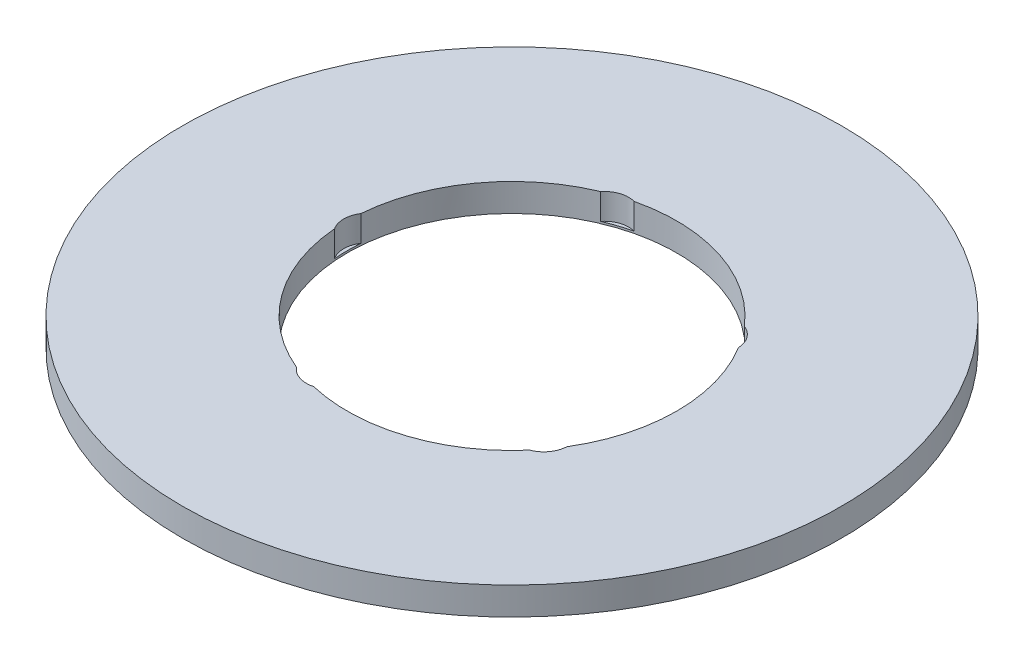
SolidWorks part; units mm, degrees
ref_plane "Front Plane" through (0, 0, 0) normal (0, 0, 1) x (1, 0, 0)
ref_plane "Top Plane" through (0, 0, 0) normal (0, 1, 0) x (1, 0, 0)
ref_plane "Right Plane" through (0, 0, 0) normal (1, 0, 0) x (0, 0, -1)
sketch "Sketch1" plane through (0, 0, 0) normal (0, 1, 0) x (1, 0, 0)
  circle A0 centre (0, 0) radius 95
  dimension "FLANGE_OD" = 190
extrude "Boss-Extrude1" add sketch "Sketch1" along normal blind 8
sketch "Sketch2" plane through (0, 0, 0) normal (0, 1, 0) x (1, 0, 0)
  circle A0 centre (0, 0) radius 47.5
  dimension "BORE_D" = 95
extrude "Cut-Extrude1" cut sketch "Sketch2" along normal through all
sketch "Sketch3" plane through (0, 8, 0) normal (0, 1, 0) x (1, 0, 0)
  circle A0 centre (0, 0) radius 41.4918 construction
  circle A1 centre (-41.4918, 0) radius 6.9915
  dimension "BOLT_D" = 13.983
  dimension "BOLT_PCD" = 82.9835
extrude "Cut-Extrude2" cut sketch "Sketch3" against normal blind 7.4347
pattern_circular "CirPattern1" count 5 over 360 about axis through (0, 0, 0) along (0, 1, 0) of "Cut-Extrude2"
